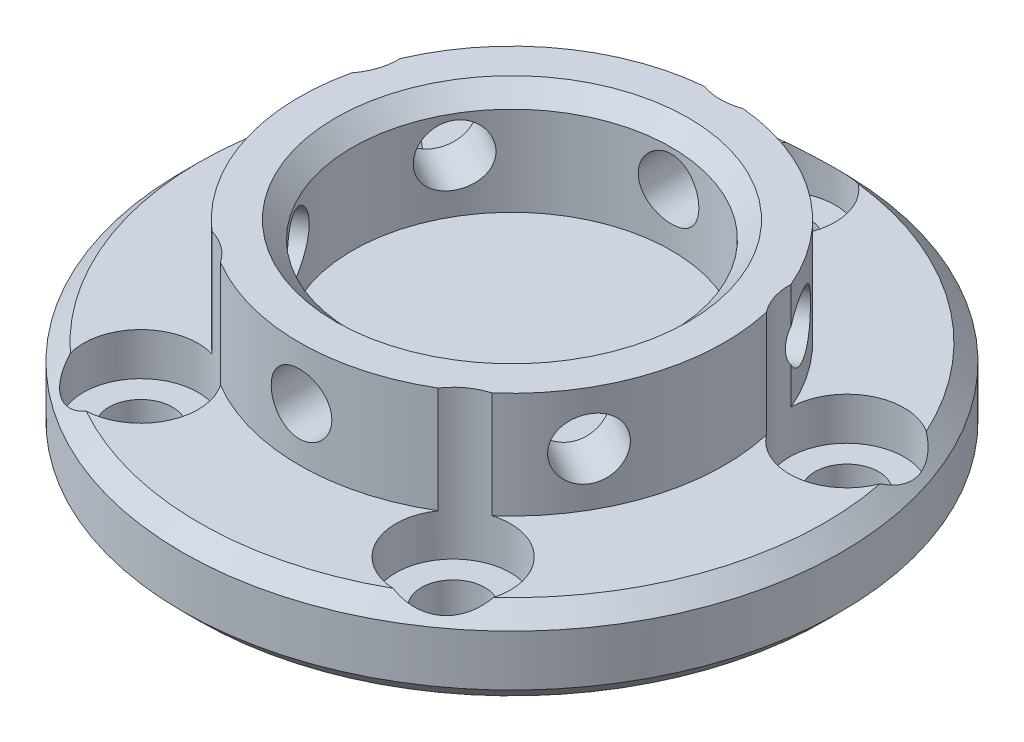
SolidWorks part; units mm, degrees
ref_plane "前视基准面" through (0, 0, 0) normal (0, 0, 1) x (1, 0, 0)
ref_plane "上视基准面" through (0, 0, 0) normal (0, 1, 0) x (1, 0, 0)
ref_plane "右视基准面" through (0, 0, 0) normal (1, 0, 0) x (0, 0, -1)
other "Configuration Table"
sketch "草图1" plane through (0, 0, 0) normal (0, 1, 0) x (1, 0, 0)
  circle A0 centre (0, 0) radius 12.5 construction
  circle A1 centre (0, 12.5) radius 1.5
  circle A2 centre (0, 0) radius 15.5
  circle A3 centre (11.8882, 3.8627) radius 1.5
  circle A4 centre (7.3473, -10.1127) radius 1.5
  circle A5 centre (-7.3473, -10.1127) radius 1.5
  circle A6 centre (-11.8882, 3.8627) radius 1.5
  point P18 (0, 0)
  dimension "D1" = 25
  dimension "D2" = 3
  dimension "D3" = 31
  dimension "D4" = 5
extrude "凸台-拉伸1" add sketch "草图1" along normal blind 4
sketch "草图2" plane through (0, 4, 0) normal (0, 1, 0) x (1, 0, 0)
  circle A0 centre (0, 0) radius 7.5
  circle A1 centre (0, 0) radius 10
  dimension "D1" = 15
  dimension "D2" = 20
extrude "凸台-拉伸2" add sketch "草图2" along normal blind 5
ref_plane "基准面1" through (0, 2, 0) normal (0, 1, 0) x (1, 0, 0)
sketch "草图5" plane through (0, 2, 0) normal (0, 1, 0) x (1, 0, 0)
  circle A0 centre (0, 12.5) radius 2.7
  circle A1 centre (11.8882, 3.8627) radius 2.7
  circle A2 centre (7.3473, -10.1127) radius 2.7
  circle A3 centre (-7.3473, -10.1127) radius 2.7
  circle A4 centre (-11.8882, 3.8627) radius 2.7
  point P14 (0, 0)
  dimension "D1" = 5
extrude "切除-拉伸3" cut sketch "草图5" along normal through all
sketch "草图6" plane through (0, 0, 0) normal (0, 0, 1) x (1, 0, 0)
  line L0 (0, 12.3571) -> (0, -3.1552) construction
  line L1 (10, 6.5) -> (-10, 6.5) construction
  line L2 (10, 4) -> (10, 9) construction
  line L3 (-10, 9) -> (-10, 4) construction
  line L4 (0, 9) -> (0, 4) construction
  circle A0 centre (0, 6.5) radius 1.425
  dimension "D1" = 2.85
extrude "切除-拉伸4" cut sketch "草图6" against normal mid plane 40
pattern_circular "阵列(圆周)2" count 3 every 120 about axis through (0, 9, 0) along (0, 1, 0) of "切除-拉伸4"
chamfer "倒角1" distance 0.8 angle 45 3 edges at (0, 0, 15.5) (0, 4, 15.5) (0, 9, 7.5)
